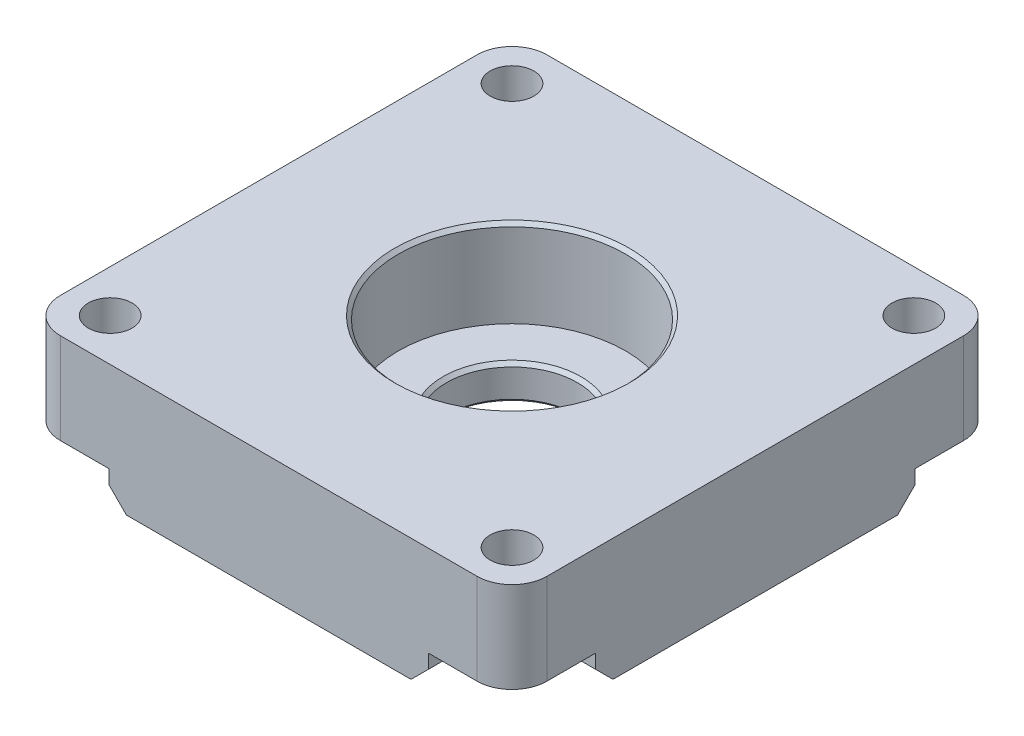
SolidWorks part; units mm, degrees
ref_plane "Спереди" through (0, 0, 0) normal (0, 0, 1) x (1, 0, 0)
ref_plane "Сверху" through (0, 0, 0) normal (0, 1, 0) x (1, 0, 0)
ref_plane "Справа" through (0, 0, 0) normal (1, 0, 0) x (0, 0, -1)
sketch "Эскиз1" plane through (0, 0, 0) normal (0, 1, 0) x (1, 0, 0)
  line L0 (-13.925, 13.925) -> (13.925, 13.925)
  line L1 (-13.925, -13.925) -> (-13.925, 13.925)
  line L3 (13.925, -13.925) -> (13.925, 13.925)
  line L4 (15.3075, 0) -> (13.925, 0) construction
  line L5 (13.925, -13.925) -> (-13.925, -13.925)
  line L7 (-11.5, -11.5) -> (11.5, -11.5) construction
  line L8 (-11.5, -11.5) -> (-11.5, 11.5) construction
  line L9 (-11.5, 11.5) -> (11.5, 11.5) construction
  line L10 (11.5, -11.5) -> (11.5, 11.5) construction
  line L11 (-11.5, -11.5) -> (11.5, 11.5) construction
  line L12 (-11.5, 11.5) -> (11.5, -11.5) construction
  line L14 (13.925, 9.1449) -> (11.1449, 9.1449)
  line L15 (9.1449, 13.925) -> (9.1449, 11.1449)
  line L16 (0, 13.925) -> (0, 16.4858) construction
  line L18 (-13.925, 9.1449) -> (-11.1449, 9.1449)
  line L19 (-9.1449, 13.925) -> (-9.1449, 11.1449)
  line L22 (-9.1449, -13.925) -> (-9.1449, -11.1449)
  line L23 (-13.925, -9.1449) -> (-11.1449, -9.1449)
  line L25 (9.1449, -13.925) -> (9.1449, -11.1449)
  line L26 (13.925, -9.1449) -> (11.1449, -9.1449)
  circle A0 centre (-11.5, 11.5) radius 1.25
  circle A1 centre (11.5, 11.5) radius 1.25
  circle A2 centre (-11.5, -11.5) radius 1.25
  circle A3 centre (11.5, -11.5) radius 1.25
  circle A8 centre (0, 0) radius 3.75
  arc A9 (11.1449, 9.1449) -> (9.1449, 11.1449) centre (11.1449, 11.1449) cw
  arc A10 (-11.1449, 9.1449) -> (-9.1449, 11.1449) centre (-11.1449, 11.1449) ccw
  arc A11 (-11.1449, -9.1449) -> (-9.1449, -11.1449) centre (-11.1449, -11.1449) cw
  arc A12 (11.1449, -9.1449) -> (9.1449, -11.1449) centre (11.1449, -11.1449) ccw
  point P0 (0, 0)
  point P8 (0, 0)
  point P28 (9.1449, 9.1449)
  point P51 (9.1449, -9.1449)
  dimension "D1" = 27.85
  dimension "D2" = 2
  dimension "D4" = 7.5
  dimension "D3" = 23
extrude "Бобышка-Вытянуть1" add sketch "Эскиз1" along normal blind 7 contours L3 L0 L1 L5 A8 | A2 | A3 | A1 | A0 region at (-11.5349, 0, -13.8574) region at (0, 0, -13.5311) region at (11.5349, 0, -13.8574) region at (-12.5349, 0, 9.2125) region at (13.8574, 0, 11.5349)
extrude "Вырез-Вытянуть1" cut sketch "Эскиз1<4>" along normal blind 1.8 contours A2 | A3 | A1 | A0 region at (-11.5349, 0, -13.8574) region at (11.5349, 0, -13.8574) region at (-12.5349, 0, 9.2125) region at (13.8574, 0, 11.5349)
sketch "Эскиз1<4>" plane through (0, 0, 0) normal (0, 1, 0) x (1, 0, 0) same geometry as "Эскиз1"
chamfer "Фаска1" distance 1 angle 45 12 edges at (9.1449, 0, 12.5349) (9.7307, 0, 9.7307) (12.5349, 0, 9.1449) (12.5349, 0, -9.1449) (9.7307, 0, -9.7307) (9.1449, 0, -12.5349) (-12.5349, 0, 9.1449) (-9.1449, 0, 12.5349) (-9.7307, 0, 9.7307) (-9.1449, 0, -12.5349) (-12.5349, 0, -9.1449) (-9.7307, 0, -9.7307)
fillet "Скругление1" radius 2 4 edges at (-13.925, 4.4, -13.925) (-13.925, 4.4, 13.925) (13.925, 4.4, 13.925) (13.925, 4.4, -13.925)
sketch "Эскиз3" plane through (0, 7, 0) normal (0, 1, 0) x (1, 0, 0)
  circle A0 centre (0, 0) radius 6.5
extrude "Вырез-Вытянуть2" cut sketch "Эскиз3" against normal blind 5
chamfer "Фаска2" distance 0.2 angle 45 3 edges at (0, 2, 3.75) (0, 7, 6.5) (0, 0, 3.75)
